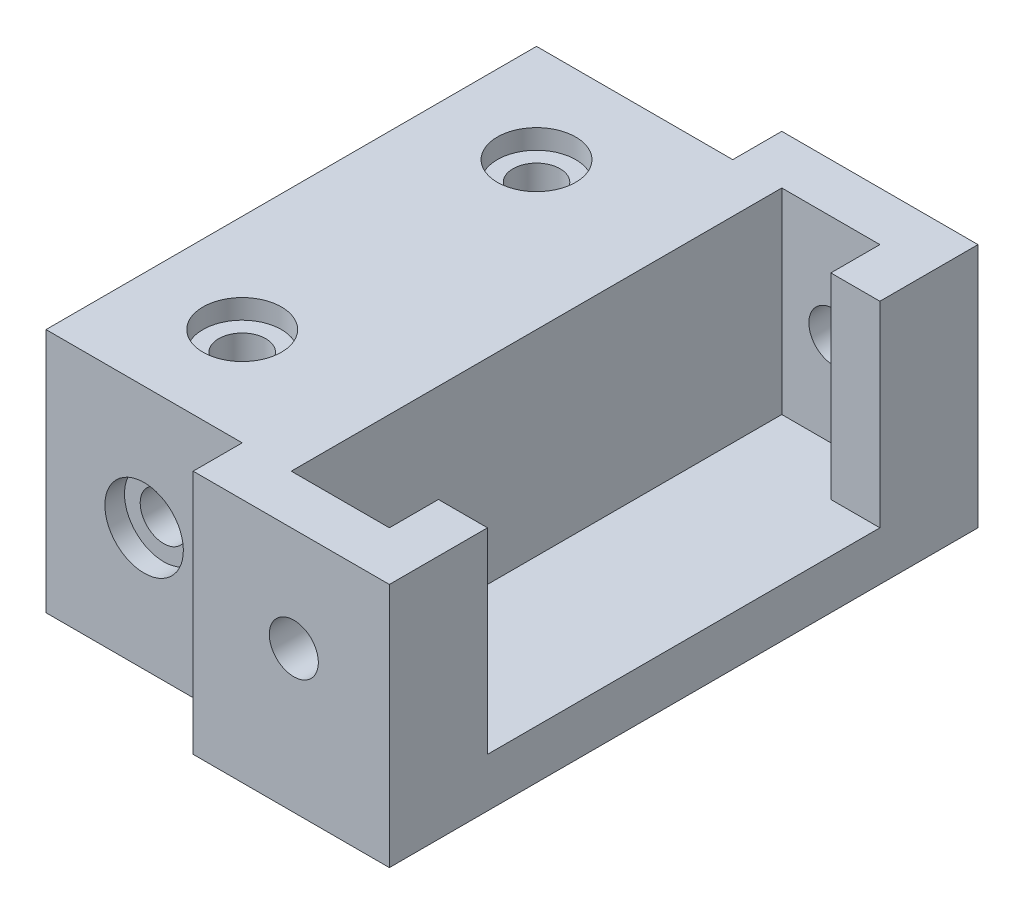
SolidWorks part; units mm, degrees
ref_plane "Plan de face" through (0, 0, 0) normal (0, 0, 1) x (1, 0, 0)
ref_plane "Plan de dessus" through (0, 0, 0) normal (0, 1, 0) x (1, 0, 0)
ref_plane "Plan de droite" through (0, 0, 0) normal (1, 0, 0) x (0, 0, -1)
sketch "Esquisse1" plane through (0, 0, 0) normal (0, 1, 0) x (1, 0, 0)
  line L0 (5, 5) -> (5, 55)
  line L1 (0, 0) -> (20, 0)
  line L2 (0, 0) -> (0, 60)
  line L3 (0, 60) -> (20, 60)
  line L4 (20, 0) -> (20, 60)
  line L5 (5, 55) -> (15, 55)
  line L6 (15, 5) -> (15, 55)
  line L7 (5, 5) -> (15, 5)
  line L9 (0, 0) -> (20, 0)
  line L10 (0, 0) -> (0, 10)
  line L11 (0, 10) -> (20, 10)
  line L12 (20, 0) -> (20, 10)
  line L13 (20, 60) -> (0, 60)
  line L14 (20, 60) -> (20, 50)
  line L15 (20, 50) -> (0, 50)
  line L16 (0, 60) -> (0, 50)
  dimension "D1" = 20
  dimension "D2" = 60
  dimension "D4" = 10
  dimension "D5" = 10
  dimension "D3" = 5
extrude "Boss.-Extru.1" add sketch "Esquisse1" along normal blind 20 contours L0 L15 L2 L11 | L15 L4 L3 L2 L0 L5 L6 | L11 L2 L1 L4 L6 L7 L0 region at (10, 0, -4.1667) region at (2.5, 0, -30) region at (10, 0, -55.8333)
extrude "Boss.-Extru.2" add sketch "Esquisse1<3>" against normal blind 5 contours L15 L4 L3 L2 L0 L5 L6 | L4 L15 L6 L11 | L15 L6 L5 L0 | L6 L15 L0 L11 | L0 L15 L2 L11 | L11 L2 L1 L4 L6 L7 L0 | L11 L0 L7 L6 region at (10, 0, -4.1667) region at (10, 0, -7.5) region at (2.5, 0, -30) region at (10, 0, -30) region at (10, 0, -55.8333) region at (10, 0, -52.5) region at (17.5, 0, -30)
sketch "Esquisse1<3>" plane through (0, 0, 0) normal (0, 1, 0) x (1, 0, 0) same geometry as "Esquisse1"
sketch "Esquisse3" plane through (0, 0, 0) normal (-1, 0, 0) x (0, 0, 1)
  line L1 (-55, -5) -> (-50, -5)
  line L2 (-55, -5) -> (-55, 20)
  line L3 (-55, 20) -> (-50, 20)
  line L4 (-60, 20) -> (-60, -5)
  line L5 (-60, -5) -> (0, -5)
  line L6 (0, -5) -> (0, 20)
  line L7 (0, 20) -> (-60, 20)
  line L8 (-60, 20) -> (-60, -5)
  line L9 (-60, -5) -> (0, -5)
  line L10 (0, -5) -> (0, 20)
  line L11 (0, 20) -> (-60, 20)
  line L12 (-50, -5) -> (-50, 20)
  line L13 (-5, -5) -> (-10, -5)
  line L14 (-5, -5) -> (-5, 20)
  line L15 (-5, 20) -> (-10, 20)
  line L16 (-10, -5) -> (-10, 20)
  line L17 (-50, 20) -> (-10, 20)
  line L18 (-50, 20) -> (-50, 15)
  line L19 (-50, 15) -> (-10, 15)
  line L20 (-10, 20) -> (-10, 15)
  line M10 (-60, -5) -> (0, -5)
  line M12 (0, 20) -> (-60, 20)
  dimension "D2" = 5
  dimension "D3" = 5
  dimension "D4" = 5
  dimension "D5" = 5
  dimension "D6" = 5
  dimension "D1" = 0
extrude "Boss.-Extru.3" add sketch "Esquisse3" along normal blind 20 contours L12 L2 M10 M12 | L16 L9 L14 L11 | L12 L19 L16 M12 region at (0, 7.5, -52.5) region at (0, 7.5, -7.5) region at (0, 17.5, -30)
sketch "Esquisse4" plane through (0, 0, 0) normal (0, 0, 1) x (1, 0, 0)
  line L0 (5, 20) -> (15, 0)
  line L4 (0, 20) -> (0, -5)
  line L5 (0, -5) -> (20, -5)
  line L6 (20, -5) -> (20, 20)
  line L7 (20, 20) -> (0, 20)
  line L8 (0, 20) -> (0, -5)
  line L9 (0, -5) -> (20, -5)
  line L10 (20, -5) -> (20, 20)
  line L11 (20, 20) -> (0, 20)
  line L12 (5, 0) -> (15, 0)
  line L13 (15, 0) -> (15, 20)
  line L14 (15, 20) -> (5, 20)
  line L15 (5, 20) -> (5, 0)
  line L16 (5, 0) -> (15, 0)
  line L17 (15, 0) -> (15, 20)
  line L18 (15, 20) -> (5, 20)
  line L19 (5, 20) -> (5, 0)
  circle A0 centre (10.2594, 9.4811) radius 2.5
  dimension "D3" = 5
  dimension "D1" = 0
  dimension "D2" = 0
extrude "Enlèv. mat.-Extru.2" cut sketch "Esquisse4" along normal blind 40 and the other way through all contours L0 A0 | L0 A0 region at (11.2084, 9.9556, 0) region at (9.3104, 9.0066, 0)
sketch "Esquisse5" plane through (0, 20, 0) normal (0, 1, 0) x (1, 0, 0)
  line L0 (-10, 55) -> (-10, 5)
  line L1 (-20, 55) -> (0, 55) construction
  line L2 (-20, 5) -> (0, 5) construction
  point P6 (-10, 45)
  point P7 (-10, 15)
  dimension "D1" = 10
  dimension "D2" = 10
sketch "Esquisse6" plane through (0, 0, -5) normal (0, 0, 1) x (1, 0, 0)
  line L0 (-10, 20) -> (-10, -5)
  line L1 (-20, 20) -> (0, 20) construction
  line L2 (-20, -5) -> (0, -5) construction
  point P6 (-10, 7.5)
sketch "Esquisse7" plane through (0, 0, -55) normal (0, 0, -1) x (-1, 0, 0)
  point P0 (10, 7.5)
hole_wizard "Chambrage pour vis à six pans creux M41" positions "Esquisse3D1" profile "Esquisse8" counterbore size "M4" standard "ISO" end condition through all
sketch3d "Esquisse3D1"
  point P0 (-10, 7.5, -5)
  point P3 (-10, 20, -45)
  point P6 (-10, 7.5, -55)
  point P10 (-10, 20, -15)
sketch "Esquisse8" plane through (-10, 7.5, -5) normal (1, 0, 0) x (0, -1, 0)
  line L0 (0, 0) -> (0, 55)
  line L1 (0, 55) -> (2.4, 55)
  line L3 (2.4, 55) -> (2.4, 2)
  line L4 (2.4, 2) -> (4, 2)
  line L5 (4, 2) -> (4, 0)
  line L7 (4, 0) -> (0, 0)
  line L11 (0, -6.35) -> (0, 107.95) construction
  dimension "Diamètre du perçage jusqu'au prochain" = 4.8
  dimension "Profondeur du perçage jusqu'au prochain" = 55
  dimension "Diamètre du chambrage" = 8
  dimension "Profondeur du chambrage" = 2
